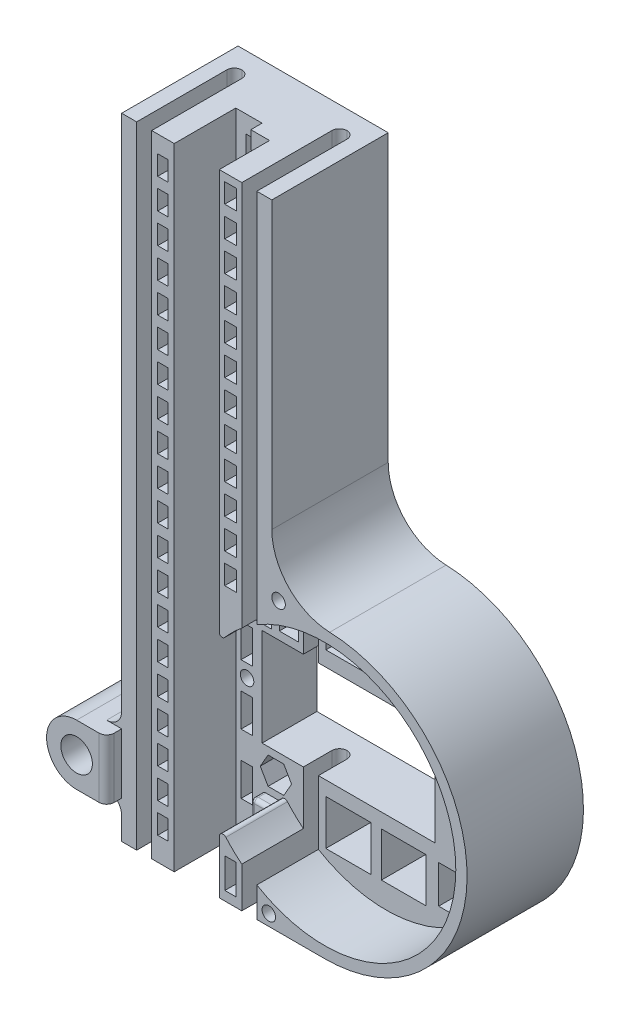
SolidWorks part; units mm, degrees
material "201 Geglühter Edelstahl (SS)"
ref_plane "Ebene vorne" through (0, 0, 0) normal (0, 0, 1) x (1, 0, 0)
ref_plane "Ebene oben" through (0, 0, 0) normal (0, 1, 0) x (1, 0, 0)
ref_plane "Ebene rechts" through (0, 0, 0) normal (1, 0, 0) x (0, 0, -1)
sketch "BodyBase" plane through (0, 0, 0) normal (0, 0, 1) x (1, 0, 0)
  line L0 (0, -19) -> (-56.6713, -19) construction
  line L1 (-27, 66) -> (-7, 66)
  line L2 (0, -19) -> (-27, -19)
  line L3 (-27, -19) -> (-27, 66)
  line L4 (-7, 66) -> (-7, 19)
  line L5 (-7, 19) -> (0, 19)
  circle A0 centre (0, 0) radius 19
  dimension "D1" = 38
  dimension "D2" = 27
  dimension "D3" = 20
  dimension "D4" = 7
  dimension "D5" = 85
extrude "body" add sketch "BodyBase" along normal mid plane 15.5 contours A0 L5 L4 L1 L3 L2 | A0 region at (-18.0553, 28.5573, 0) region at (0, 0, 0)
sketch "ServoLoch" plane through (0, 0, 7.75) normal (0, 0, 1) x (1, 0, 0)
  line L2 (-16.5, 6.5) -> (6.5, 6.5)
  line L4 (-16.5, 6.5) -> (-16.5, -6.5)
  line L5 (-16.5, -6.5) -> (6.5, -6.5)
  line L6 (6.5, 6.5) -> (6.5, -6.5)
  line L7 (-16.5, 6.5) -> (6.5, -6.5) construction
  line L8 (-16.5, -6.5) -> (6.5, 6.5) construction
  point P0 (-5, 0)
  dimension "D1" = 5
  dimension "D2" = 13
  dimension "D3" = 23
extrude "servo_loch" cut sketch "ServoLoch" against normal through all
sketch "Zahradlauf" plane through (0, 0, 7.75) normal (0, 0, 1) x (1, 0, 0)
  circle A0 centre (0, 0) radius 17.5
  dimension "D1" = 35
extrude "zahnrad_lauf" cut sketch "Zahradlauf" against normal blind 8.2
sketch "zahnstangenlauf" plane through (0, 0, 7.75) normal (0, 0, 1) x (1, 0, 0)
  line L1 (-27, 66) -> (-7, 66) construction
  line L2 (0, -19) -> (-27, -19) construction
  line L4 (-7, 66) -> (-7, 19) construction
  line L5 (-20, 66) -> (-14, 66)
  line L6 (-20, 66) -> (-20, -19)
  line L7 (-20, -19) -> (-14, -19)
  line L8 (-14, 66) -> (-14, -19)
  dimension "D1" = 6
  dimension "D2" = 7
  dimension "D3" = 7
extrude "zahnstangen_lauf" cut sketch "zahnstangenlauf" against normal blind 8.2
sketch "Skizze5" plane through (0, 0, -0.45) normal (0, 0, 1) x (1, 0, 0)
  line L0 (-20, -19) -> (-14, -19) construction
  line L1 (-16.5, -12) -> (-14, -12)
  line L2 (-16.5, -12) -> (-16.5, -19)
  line L3 (-16.5, -19) -> (-14, -19)
  line L4 (-14, -12) -> (-14, -19)
  line L5 (-14, -19) -> (-14, -10.5) construction
  dimension "D1" = 7
  dimension "D2" = 2.5
extrude "frontfuehrung" add sketch "Skizze5" along normal blind 1.5
sketch "Skizze2" plane through (0, 0, -0.45) normal (0, 0, 1) x (1, 0, 0)
  line L0 (-14, 66) -> (-20, 66) construction
  line L1 (-16.5, 66) -> (-14, 66)
  line L2 (-16.5, 66) -> (-16.5, 12.0413)
  line L3 (-16.5, 12.0413) -> (-14, 12.0413)
  line L4 (-14, 66) -> (-14, 12.0413)
  line L5 (-14, 10.5) -> (-14, 66) construction
  dimension "D1" = 2.5
extrude "Aufsatz-Linear austragen2" add sketch "Skizze2" along normal blind 1.5
fillet "Verrundung22" radius 0.5 1 edges at (-14, -10.5, 3.65)
fillet "Verrundung13" radius 8 1 edges at (-7, 19, 0)
sketch "SkizzeFurche" plane through (0, 0, 7.75) normal (0, 0, 1) x (1, 0, 0)
  line L0 (-20, -19) -> (-27, -19) construction
  line L1 (-25, -19) -> (-23, -19)
  line L2 (-25, -19) -> (-25, 66)
  line L3 (-25, 66) -> (-23, 66)
  line L4 (-23, -19) -> (-23, 66)
  line L5 (-27, 66) -> (-20, 66) construction
  line L6 (-27, -19) -> (-27, 66) construction
  line L7 (-20, 66) -> (-20, -19) construction
  line L8 (-14, 66) -> (-7, 66) construction
  line L9 (-11, 66) -> (-9, 66)
  line L10 (-11, 66) -> (-11, -19)
  line L11 (-11, -19) -> (-9, -19)
  line L12 (-9, 66) -> (-9, -19)
  line L13 (-14, 10.5) -> (-14, 66) construction
  line L14 (-7, 66) -> (-7, 26.9815) construction
  line L15 (0, -19) -> (-14, -19) construction
  dimension "D1" = 2
  dimension "D2" = 3
  dimension "D3" = 3
  dimension "D4" = 2
extrude "Furche" cut sketch "SkizzeFurche" against normal blind 13
sketch "gegenstuckInnen" plane through (0, 0, -5.25) normal (0, 0, 1) x (1, 0, 0)
  line L0 (-11, 66) -> (-11, 13.6107) construction
  line L1 (-11, 45.64) -> (-9, 45.64)
  line L2 (-11, 45.64) -> (-11, 41.04)
  line L3 (-11, 41.04) -> (-9, 41.04)
  line L4 (-9, 45.64) -> (-9, 41.04)
  line L5 (-9, 6.5) -> (-9, 66) construction
  line L6 (-9, 66) -> (-11, 66) construction
  point P8 (-10, 66)
  dimension "D1" = 4.6
  dimension "D2" = 20.36
extrude "gegenstuck innen" add sketch "gegenstuckInnen" along normal blind 8
pattern_linear "Lineares Muster1" count 3 spacing 10 along (0, -1, 0) of "gegenstuck innen"
sketch "Skizze13" plane through (0, 0, 0) normal (0, 0, 1) x (1, 0, 0)
  line L0 (-27, -14) -> (-31, -14)
  line L1 (-27, -6) -> (-31, -6)
  line L2 (-27, -6) -> (-27, -14)
  line L3 (-27, -19) -> (-27, 66) construction
  arc A0 (-31, -6) -> (-31, -14) centre (-31, -10) ccw
  dimension "D1" = 4
  dimension "D2" = 8
  dimension "D3" = 5
extrude "Ansatz" add sketch "Skizze13" along normal mid plane 15.5 separate body
fillet "Verrundung14" radius 2 6 edges at (-10, 45.64, 2.75) (-10, 41.04, 2.75) (-10, 35.64, 2.75) (-10, 31.04, 2.75) (-10, 25.64, 2.75) (-10, 21.04, 2.75)
sketch "gegenstuck2" plane through (0, 0, -5.25) normal (0, 0, 1) x (1, 0, 0)
  line L0 (-25, 66) -> (-25, -19) construction
  line L1 (-25, 45.85) -> (-23, 45.85)
  line L2 (-25, 45.85) -> (-25, 41.25)
  line L3 (-25, 41.25) -> (-23, 41.25)
  line L4 (-23, 45.85) -> (-23, 41.25)
  line L5 (-23, -19) -> (-23, 66) construction
  line L6 (-23, 66) -> (-25, 66) construction
  point P8 (-24, 66)
  dimension "D1" = 4.6
  dimension "D2" = 20.15
extrude "gegenstuckAussen" add sketch "gegenstuck2" along normal blind 8
pattern_linear "buckelmuster2" count 6 spacing 10 along (0, -1, 0) of "gegenstuckAussen"
fillet "Verrundung15" radius 2 12 edges at (-24, -8.75, 2.75) (-24, -4.15, 2.75) (-24, 1.25, 2.75) (-24, 5.85, 2.75) (-24, 11.25, 2.75) (-24, 15.85, 2.75) (-24, 21.25, 2.75) (-24, 25.85, 2.75) (-24, 31.25, 2.75) (-24, 35.85, 2.75) (-24, 45.85, 2.75) (-24, 41.25, 2.75)
fillet "Verrundung21" radius 0.5 1 edges at (-15.25, -12, 1.05)
sketch "bohrung oben" plane through (0, 0, 7.75) normal (0, 0, 1) x (1, 0, 0)
  line L0 (-27, -19) -> (-27, 66) construction
  line L1 (0, -19) -> (-9, -19) construction
  circle A0 centre (-7.4, -17.5) radius 0.9
  circle A1 centre (-6.1, 19.2) radius 0.9
  dimension "D1" = 1.8
  dimension "D4" = 20.9
  dimension "D6" = 1.8
  dimension "D2" = 19.6
  dimension "D3" = 1.5
  dimension "D5" = 38.2
extrude "bohrlocher oben" cut sketch "bohrung oben" against normal blind 10
sketch "Skizze11" plane through (0, 0, 7.75) normal (0, 0, 1) x (1, 0, 0)
  line L0 (-21.5, 66) -> (-21.5, -19) construction
  line L1 (-23, 66) -> (-20, 66) construction
  line L2 (-20, -19) -> (-23, -19) construction
  line L4 (-22.2, 62.7243) -> (-20.8, 62.7243)
  line L5 (-22.2, 62.7243) -> (-22.2, 60.1243)
  line L6 (-22.2, 60.1243) -> (-20.8, 60.1243)
  line L7 (-20.8, 62.7243) -> (-20.8, 60.1243)
  line L8 (-22.2, 62.7243) -> (-20.8, 60.1243) construction
  line L9 (-22.2, 60.1243) -> (-20.8, 62.7243) construction
  point P7 (-21.5, 61.4243)
  dimension "D1" = 2.6
  dimension "D2" = 1.4
extrude "Schnitt-Linear austragen5" cut sketch "Skizze11" against normal blind 15
pattern_linear "Lineares Muster3" count 20 spacing 4 along (0, -1, 0) of "Schnitt-Linear austragen5"
sketch "Skizze15" plane through (0, 0, 7.75) normal (0, 0, 1) x (1, 0, 0)
  line L0 (-27, -6) -> (-27, -14)
  line L3 (-27, -14) -> (-31, -14)
  line L8 (-27, -14) -> (-27, -6)
  line L9 (-27, -6) -> (-31, -6)
  line L10 (-31, -14) -> (-27, -14)
  line L12 (-27, -6) -> (-31, -6)
  arc A0 (-31, -6) -> (-31, -14) centre (-31, -10) ccw
  arc A2 (-31, -6) -> (-31, -14) centre (-31, -10) ccw
  dimension "D1" = 0
extrude "Ansatz oben" add sketch "Skizze15" along normal blind 2
fillet "Verrundung23" radius 2 1 edges
fillet "Verrundung24" radius 2 1 edges
fillet "Verrundung25" radius 1 1 edges at (-27, -10, 9.75)
sketch "Skizze16" plane through (0, 0, 9.75) normal (0, 0, 1) x (1, 0, 0)
  line L0 (-31, -6) -> (-31, -14) construction
  line L1 (-28, -6) -> (-31, -6) construction
  line L2 (-35, -10) -> (-31, -10) construction
  arc A0 (-31, -6) -> (-31, -14) centre (-31, -10) ccw construction
  circle A1 centre (-31, -10) radius 2.1
  dimension "D1" = 4.2
extrude "aussenborder" cut sketch "Skizze16" against normal through all
sketch "Skizze17" plane through (0, 0, 1.05) normal (0, 0, 1) x (1, 0, 0)
  line L1 (-18.6458, 60.0784) -> (-15.2458, 60.0784)
  line L2 (-18.6458, 60.0784) -> (-18.6458, 62.6784)
  line L3 (-18.6458, 62.6784) -> (-15.2458, 62.6784)
  line L4 (-15.2458, 60.0784) -> (-15.2458, 62.6784)
  dimension "D1" = 3.4
  dimension "D2" = 2.6
extrude "Schnitt-Linear austragen7" cut sketch "Skizze17" against normal blind 8
pattern_linear "Lineares Muster5" count 13 spacing 4.4 along (0, -1, 0) of "Schnitt-Linear austragen7"
sketch "Skizze18" plane through (0, 0, 7.75) normal (0, 0, 1) x (1, 0, 0)
  line L0 (-12.5, 66) -> (-12.5, 12.4711) construction
  line L1 (-14, 66) -> (-11, 66) construction
  line L3 (-13.2764, 61.3654) -> (-11.7236, 61.3654)
  line L4 (-13.2764, 61.3654) -> (-13.2764, 63.9654)
  line L5 (-13.2764, 63.9654) -> (-11.7236, 63.9654)
  line L6 (-11.7236, 61.3654) -> (-11.7236, 63.9654)
  line L7 (-13.2764, 61.3654) -> (-11.7236, 63.9654) construction
  line L8 (-13.2764, 63.9654) -> (-11.7236, 61.3654) construction
  point P4 (-12.5, 62.6654)
  dimension "D1" = 2.6
  dimension "D2" = 1.5528
extrude "Schnitt-Linear austragen8" cut sketch "Skizze18" against normal blind 14
pattern_linear "Lineares Muster6" count 12 spacing 4 along (0, -1, 0) of "Schnitt-Linear austragen8"
sketch "Skizze22" plane through (0, 0, -0.45) normal (0, 0, 1) x (1, 0, 0)
  line L1 (-12.5695, -9.2794) -> (-13.613, -7.4721)
  line L2 (-13.613, -7.4721) -> (-15.6999, -7.4721)
  line L3 (-15.6999, -7.4721) -> (-16.7433, -9.2794)
  line L4 (-16.7433, -9.2794) -> (-15.6999, -11.0867)
  line L5 (-15.6999, -11.0867) -> (-13.613, -11.0867)
  line L6 (-13.613, -11.0867) -> (-12.5695, -9.2794)
  circle A0 centre (-14.6564, -9.2794) radius 1.8073 construction
extrude "Schnitt-Linear austragen10" cut sketch "Skizze22" against normal blind 6
fillet "Verrundung27" radius 0.4 1 edges at (-14, 10.5, 3.65)
fillet "Verrundung28" radius 0.4 1 edges at (-15.2458, 12.0413, 0.3)
sketch "Skizze24" plane through (0, 0, -0.45) normal (0, 0, 1) x (1, 0, 0)
  line L1 (-19.2974, 6.1187) -> (-17.7974, 6.1187)
  line L2 (-19.2974, 6.1187) -> (-19.2974, 1.7187)
  line L3 (-19.2974, 1.7187) -> (-17.7974, 1.7187)
  line L4 (-17.7974, 6.1187) -> (-17.7974, 1.7187)
  line L5 (-19.2974, 6.1187) -> (-17.7974, 1.7187) construction
  line L6 (-19.2974, 1.7187) -> (-17.7974, 6.1187) construction
  point P0 (-18.5474, 3.9187)
  dimension "D1" = 4.4
  dimension "D2" = 1.5
extrude "Schnitt-Linear austragen11" cut sketch "Skizze24" against normal blind 6
pattern_linear "Lineares Muster7" count 3 spacing 8 along (0, -1, 0) of "Schnitt-Linear austragen11"
fillet "Verrundung31" radius 1 1 edges at (-25, 55.925, -5.25)
fillet "Verrundung32" radius 1 1 edges at (-23, 55.925, -5.25)
fillet "Verrundung33" radius 1 2 edges at (-9, 55.82, -5.25) (-11, 55.82, -5.25)
fillet "Verrundung34" radius 1 4 edges at (-9, -12.75, -5.25) (-11, -12.75, -5.25) (-23, -13.875, -5.25) (-25, -13.875, -5.25)
fillet "Verrundung35" radius 1 16 edges at (-11, 38.34, -5.25) (-9, 38.34, -5.25) (-9, 28.34, -5.25) (-11, 28.34, -5.25) (-23, 38.55, -5.25) (-25, 38.55, -5.25) (-23, 28.55, -5.25) (-25, 28.55, -5.25) (-23, 18.55, -5.25) (-25, 18.55, -5.25) (-25, 8.55, -5.25) (-23, 8.55, -5.25) (-23, -1.45, -5.25) (-25, -1.45, -5.25) (-9, 13.77, -5.25) (-11, 13.77, -5.25)
sketch "Skizze26" plane through (0, 0, 7.75) normal (0, 0, 1) x (1, 0, 0)
  line L1 (-13.2556, -17.7756) -> (-11.7556, -17.7756)
  line L2 (-13.2556, -17.7756) -> (-13.2556, -13.7756)
  line L3 (-13.2556, -13.7756) -> (-11.7556, -13.7756)
  line L4 (-11.7556, -17.7756) -> (-11.7556, -13.7756)
  line L5 (-13.2556, -17.7756) -> (-11.7556, -13.7756) construction
  line L6 (-13.2556, -13.7756) -> (-11.7556, -17.7756) construction
  point P0 (-12.5056, -15.7756)
  point P5 (-11.7556, -15.7756)
  point P6 (-13.2556, -15.7756)
  dimension "D1" = 1.5
  dimension "D2" = 4
extrude "Schnitt-Linear austragen13" cut sketch "Skizze26" against normal blind 13
sketch "Skizze27" plane through (0, 0, -7.75) normal (0, 0, -1) x (-1, 0, 0)
  line L0 (-16.1863, 0) -> (23.941, 0) construction
  line L1 (-6.5, -6.5) -> (-6.5, 6.5) construction
  line L2 (16.5, 6.5) -> (16.5, -6.5) construction
  circle A0 centre (-8.5, 0) radius 0.9
  circle A1 centre (18.5, 0) radius 0.9
  dimension "D1" = 1.8
  dimension "D2" = 2
  dimension "D3" = 2
extrude "Schnitt-Linear austragen14" cut sketch "Skizze27" against normal through all both and the other way through all
fillet "Verrundung30" radius 0.5 3 edges at (-16.5, -15.75, 1.05) (-16.5, -12.1464, 0.9036) (-16.5, -12, 0.05)
sketch "Skizze29" plane through (0, 0, -0.45) normal (0, 0, 1) x (1, 0, 0)
  line L0 (-9, 6.5) -> (6.5, 6.5) construction
  line L1 (-8, 14.5) -> (-2, 14.5)
  line L2 (-8, 14.5) -> (-8, 8.5)
  line L3 (-8, 8.5) -> (-2, 8.5)
  line L4 (-2, 14.5) -> (-2, 8.5)
  line L5 (-9, 6.5) -> (-9, 15.0083) construction
  line L6 (-8.0466, 8.491) -> (14.313, 8.348) construction
  line L7 (6.4061, 6.5979) -> (16.2512, 6.5349) construction
  line L8 (6.4936, -6.4838) -> (15.603, -6.5325) construction
  line L9 (-7.995, -11.4524) -> (15.2847, -11.5306) construction
  line L10 (-8.0626, 11.5205) -> (14.1493, 11.5247) construction
  line L11 (-8.9887, -8.4586) -> (14.6586, -8.5852) construction
  line L12 (6.5, -6.5) -> (-9, -6.5) construction
  line L14 (-8.017, -8.4107) -> (-2.017, -8.4107)
  line L15 (-8.017, -8.4107) -> (-8.017, -14.4107)
  line L16 (-8.017, -14.4107) -> (-2.017, -14.4107)
  line L17 (-2.017, -8.4107) -> (-2.017, -14.4107)
  line L18 (-0.5528, 14.6834) -> (5.0072, 14.6834)
  line L19 (-0.5528, 14.6834) -> (-0.5528, 8.4466)
  line L20 (-0.5528, 8.4466) -> (5.0072, 8.4466)
  line L21 (5.0072, 14.6834) -> (5.0072, 8.4466)
  line L22 (-0.5528, 14.6834) -> (5.0072, 8.4466) construction
  line L23 (-0.5528, 8.4466) -> (5.0072, 14.6834) construction
  line L24 (7.2414, 13.2281) -> (11.0073, 13.2281)
  line L25 (7.2414, 13.2281) -> (7.2414, 8.3959)
  line L26 (7.2414, 8.3959) -> (11.0073, 8.3959)
  line L27 (11.0073, 13.2281) -> (11.0073, 8.3959)
  line L28 (-0.6072, -8.4452) -> (5.3357, -8.4452)
  line L29 (-0.6072, -8.4452) -> (-0.6072, -14.3537)
  line L30 (-0.6072, -14.3537) -> (5.3357, -14.3537)
  line L31 (5.3357, -8.4452) -> (5.3357, -14.3537)
  line L32 (-0.6072, -8.4452) -> (5.3357, -14.3537) construction
  line L33 (-0.6072, -14.3537) -> (5.3357, -8.4452) construction
  line L34 (7.0166, -8.5112) -> (10.2437, -8.5112)
  line L35 (7.0166, -8.5112) -> (7.0166, -13.5494)
  line L36 (7.0166, -13.5494) -> (10.2437, -13.5494)
  line L37 (10.2437, -8.5112) -> (10.2437, -13.5494)
  line L38 (10.8119, 6.5395) -> (15.2272, 6.5395)
  line L39 (10.8119, 6.5395) -> (10.8119, -6.462)
  line L40 (10.8119, -6.462) -> (15.2272, -6.462)
  line L41 (15.2272, 6.5395) -> (15.2272, -6.462)
  point P6 (-8, 11.5)
  point P9 (-9, 10.7542)
  point P21 (-1.25, -6.5)
  point P29 (2.2272, 11.565)
  point P38 (2.3643, -11.3995)
  dimension "D1" = 2
  dimension "D2" = 1
  dimension "D4" = 2
  dimension "D5" = 6
  dimension "D6" = 6
extrude "Schnitt-Linear austragen15" cut sketch "Skizze29" against normal blind 6
sketch "Skizze30" plane through (0, 0, -0.45) normal (0, 0, 1) x (1, 0, 0)
  line L1 (-14.2027, 10.3067) -> (-11.6503, 10.3067)
  line L2 (-14.2027, 10.3067) -> (-14.2027, 7.5785)
  line L3 (-14.2027, 7.5785) -> (-11.6503, 7.5785)
  line L4 (-11.6503, 10.3067) -> (-11.6503, 7.5785)
extrude "Schnitt-Linear austragen16" cut sketch "Skizze30" against normal blind 7
sketch "Skizze31" plane through (0, 0, 7.75) normal (0, 0, 1) x (1, 0, 0)
  line L0 (-7, 66) -> (-7, 26.9815) construction
  line L1 (-27, 66) -> (-7, 66)
  line L2 (-27, 66) -> (-27, 65)
  line L3 (-27, 65) -> (-7, 65)
  line L4 (-7, 66) -> (-7, 65)
  dimension "D1" = 1
extrude "Schnitt-Linear austragen17" cut sketch "Skizze31" against normal through all
